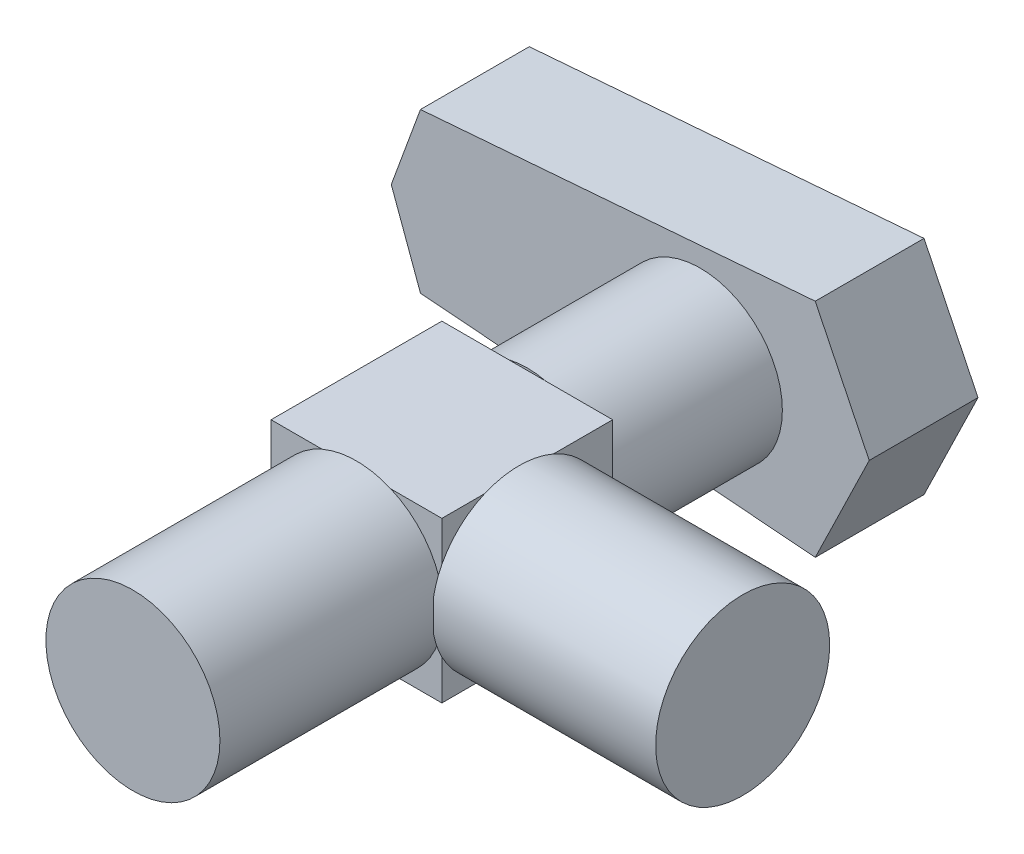
SolidWorks part; units mm, degrees
material "Brass"
ref_plane "Front Plane" through (0, 0, 0) normal (0, 0, 1) x (1, 0, 0)
ref_plane "Top Plane" through (0, 0, 0) normal (0, 1, 0) x (1, 0, 0)
ref_plane "Right Plane" through (0, 0, 0) normal (1, 0, 0) x (0, 0, -1)
sketch "Sketch2" plane through (0, 0, 0) normal (0, 1, 0) x (1, 0, 0)
  line L0 (-7.85, 7.85) -> (7.85, -7.85) construction
  line L1 (-7.85, 7.85) -> (7.85, 7.85)
  line L2 (-7.85, 7.85) -> (-7.85, -7.85)
  line L3 (-7.85, -7.85) -> (7.85, -7.85)
  line L4 (7.85, 7.85) -> (7.85, -7.85)
  line L5 (7.85, 7.85) -> (-7.85, -7.85) construction
  dimension "D1" = 15.7
  dimension "D2" = 15.7
extrude "Boss-Extrude2" add sketch "Sketch2" along normal blind 7.35 and the other way blind 7.35
sketch "Sketch3" plane through (7.85, 0, 0) normal (1, 0, 0) x (0, 0, -1)
  line L0 (7.85, -7.35) -> (7.85, 7.35) construction
  circle A0 centre (-0.75, 0) radius 8
  dimension "D2" = 16
  dimension "D1" = 8.6
extrude "Boss-Extrude3" add sketch "Sketch3" along normal blind 20.55
sketch "Sketch4" plane through (0, 0, -7.85) normal (0, 0, -1) x (-1, 0, 0)
  circle A0 centre (0, 0) radius 7.55
  dimension "D1" = 15.1
extrude "Boss-Extrude4" add sketch "Sketch4" along normal blind 25.9
sketch "Sketch5" plane through (0, 0, -33.75) normal (0, 0, -1) x (-1, 0, 0)
  line L0 (-15.5322, 0) -> (-10.5721, -10.1985)
  line L1 (-10.5721, -10.1985) -> (25.7175, -7.3136)
  line L2 (25.7175, -7.3136) -> (28.4, 0)
  line L3 (28.4, 0) -> (-15.5322, 0) construction
  line L4 (-15.5322, 0) -> (-10.5721, 10.1985)
  line L5 (-10.5721, 10.1985) -> (25.7175, 7.3136)
  line L6 (25.7175, 7.3136) -> (28.4, 0)
  point P6 (0, 0)
  dimension "D1" = 28.4
extrude "Boss-Extrude5" add sketch "Sketch5" against normal blind 10
sketch "Sketch6" plane through (0, 0, 7.85) normal (0, 0, 1) x (1, 0, 0)
  circle A0 centre (0, 0) radius 8
  dimension "D1" = 16
extrude "Boss-Extrude6" add sketch "Sketch6" along normal blind 20.55
